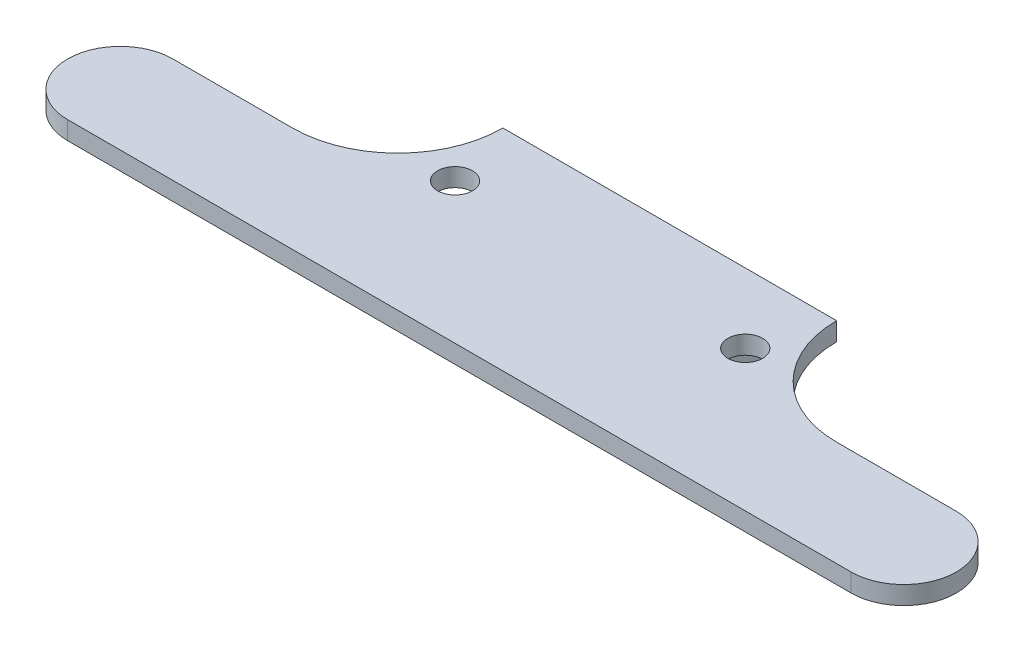
SolidWorks part; units mm, degrees
ref_plane "Front Plane" through (0, 0, 0) normal (0, 0, 1) x (1, 0, 0)
ref_plane "Top Plane" through (0, 0, 0) normal (0, 1, 0) x (1, 0, 0)
ref_plane "Right Plane" through (0, 0, 0) normal (1, 0, 0) x (0, 0, -1)
sketch "Sketch1" plane through (0, 0, 0) normal (0, 1, 0) x (1, 0, 0)
  line L0 (-34.29, 0) -> (34.29, 0) construction
  line L1 (-34.29, 4.6037) -> (34.29, 4.6038)
  line L2 (-34.29, -4.6037) -> (34.29, -4.6037)
  line L3 (-14.605, 13.8112) -> (14.605, 13.8112)
  line L4 (0, -55) -> (0, 55) construction
  arc A0 (-34.29, 4.6037) -> (-34.29, -4.6037) centre (-34.29, 0) ccw
  arc A1 (34.29, -4.6037) -> (34.29, 4.6038) centre (34.29, 0) ccw
  arc A2 (-23.8125, 4.6037) -> (-14.605, 13.8112) centre (-23.8125, 13.8112) ccw
  arc A3 (14.605, 13.8112) -> (23.8125, 4.6037) centre (23.8125, 13.8112) ccw
  circle A4 centre (-12.7, 7.7152) radius 1.524
  circle A5 centre (12.7, 7.7152) radius 1.524
  point P2 (0, 0)
  point P14 (0, 13.8112)
  dimension "D4" = 9.2075
  dimension "D8" = 3.048
  dimension "D1" = 9.2075
  dimension "D2" = 68.58
  dimension "D3" = 18.415
  dimension "D5" = 29.21
  dimension "D6" = 25.4
  dimension "D7" = 6.096
extrude "Boss-Extrude1" add sketch "Sketch1" along normal blind 1.6 contours L2 A1 L1 A0 | A3 L3 A2 L1 A4 A5 region at (0, 0, 0) region at (0, 0, -8.9636)
sketch "Sketch2" plane through (0, 0, 0) normal (0, 1, 0) x (1, 0, 0)
  line L0 (-14.605, 13.8112) -> (14.605, 13.8112) construction
  line L1 (-10.16, 6.4452) -> (10.16, 6.4452)
  line L2 (-10.16, 6.4452) -> (-10.16, 13.8112)
  line L3 (-10.16, 13.8112) -> (10.16, 13.8112)
  line L4 (10.16, 6.4452) -> (10.16, 13.8112)
  line L5 (-10.16, 6.4452) -> (10.16, 13.8112) construction
  line L6 (-10.16, 13.8112) -> (10.16, 6.4452) construction
  point P0 (0, 10.1282)
  dimension "D1" = 7.366
  dimension "D2" = 20.32
extrude "Boss-Extrude2" add sketch "Sketch2" against normal blind 3.81
